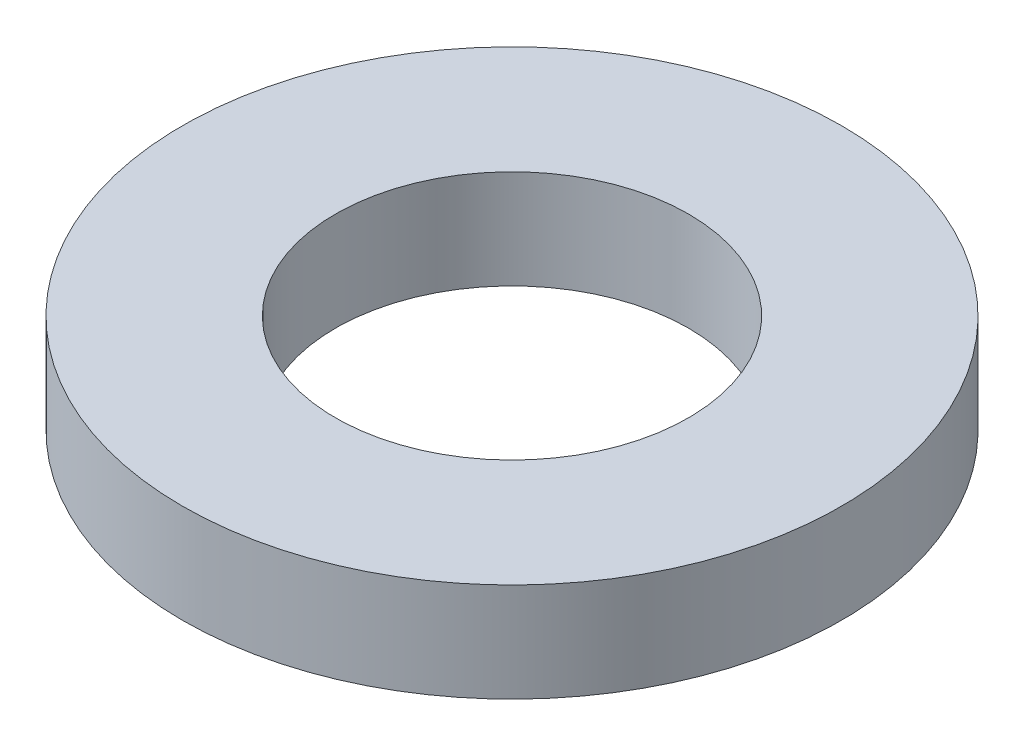
SolidWorks part; units mm, degrees
ref_plane "Front Plane" through (0, 0, 0) normal (0, 0, 1) x (1, 0, 0)
ref_plane "Top Plane" through (0, 0, 0) normal (0, 1, 0) x (1, 0, 0)
ref_plane "Right Plane" through (0, 0, 0) normal (1, 0, 0) x (0, 0, -1)
sketch "Sketch1" plane through (0, 0, 0) normal (0, 1, 0) x (1, 0, 0)
  circle A0 centre (0, 0) radius 70
  dimension "FLANGE_OD" = 140
extrude "Boss-Extrude1" add sketch "Sketch1" along normal blind 21
sketch "Sketch2" plane through (0, 0, 0) normal (0, 1, 0) x (1, 0, 0)
  circle A0 centre (0, 0) radius 37.5
  dimension "BORE_D" = 75
extrude "Cut-Extrude1" cut sketch "Sketch2" along normal through all
sketch "Sketch3" plane through (0, 21, 0) normal (0, 1, 0) x (1, 0, 0)
  circle A0 centre (0, 0) radius 32.1517 construction
  circle A1 centre (-32.1517, 0) radius 3.0193
  dimension "BOLT_D" = 6.0386
  dimension "BOLT_PCD" = 64.3034
extrude "Cut-Extrude2" cut sketch "Sketch3" against normal blind 20.4596 rebuild error yes
pattern_circular "CirPattern1" count 3 over 360 rebuild error yes
